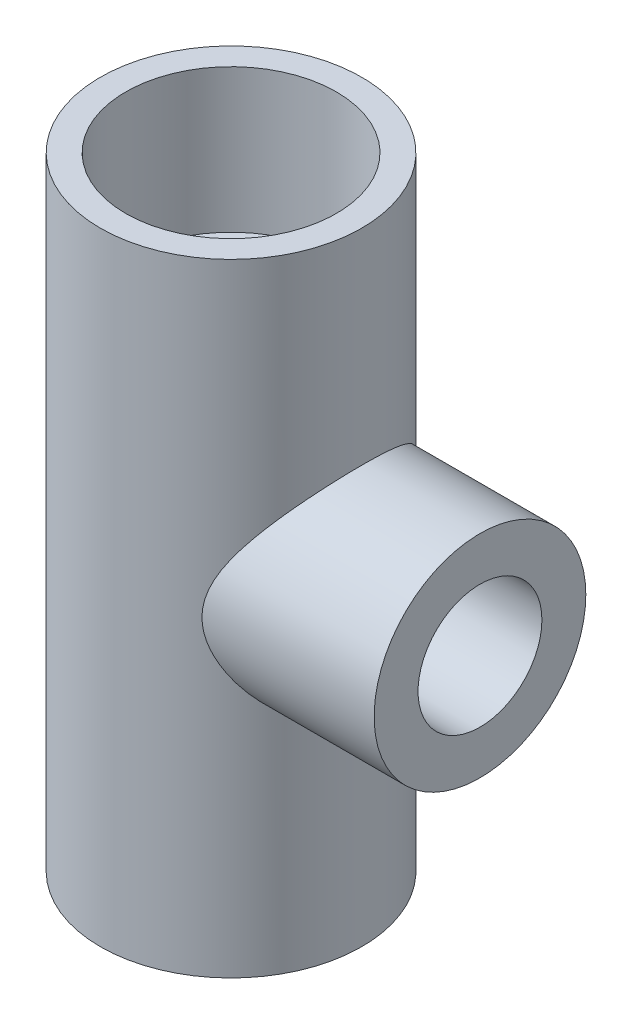
SolidWorks part; units mm, degrees
ref_plane "Front Plane" through (0, 0, 0) normal (0, 0, 1) x (1, 0, 0)
ref_plane "Top Plane" through (0, 0, 0) normal (0, 1, 0) x (1, 0, 0)
ref_plane "Right Plane" through (0, 0, 0) normal (1, 0, 0) x (0, 0, -1)
sketch "Sketch1" plane through (0, 0, 0) normal (0, 1, 0) x (1, 0, 0)
  circle A0 centre (0, 0) radius 0.6565
  circle A1 centre (0, 0) radius 0.529
  circle A2 centre (0, 0) radius 0.412
  dimension "D1" = 1.313
  dimension "D2" = 1.058
  dimension "D3" = 0.824
extrude "Boss-Extrude1" add sketch "Sketch1" along normal blind 1.5625 contours A0 A1 | A1 A2 region at (-0.6379, 0, 0) region at (-0.514, 0, 0)
extrude "Cut-Extrude1" cut sketch "Sketch1<3>" along normal blind 0.72 contours A1 A2 region at (-0.514, 0, 0)
sketch "Sketch1<3>" plane through (0, 0, 0) normal (0, 1, 0) x (1, 0, 0) same geometry as "Sketch1"
mirror "Mirror1" about plane through (0, 1.5625, 0) normal (0, 1, 0) of "Cut-Extrude1", "Boss-Extrude1"
ref_plane "Plane1" through (1.25, 0, 0) normal (1, 0, 0) x (0, 0, -1)
sketch "Sketch2" plane through (1.25, 0, 0) normal (1, 0, 0) x (0, 0, -1)
  line L0 (0, 3.125) -> (0, 0) construction
  line L1 (0.6565, 3.125) -> (-0.6565, 3.125) construction
  line L2 (-0.6565, 0) -> (0.6565, 0) construction
  circle A0 centre (0, 1.5625) radius 0.5315
  circle A1 centre (0, 1.5625) radius 0.424
  circle A2 centre (0, 1.5625) radius 0.311
  dimension "D1" = 1.063
  dimension "D2" = 0.848
  dimension "D3" = 0.622
extrude "Boss-Extrude2" add sketch "Sketch2" against normal up to surface (0.8646 mm away) contours L0 A0 A1 | L0 A1 A2 | A1 L0 A2 | A0 L0 A1 region at (1.25, 1.9299, -0.3674) region at (1.25, 2.0403, 0.0119) region at (1.25, 1.8556, -0.2931) region at (1.25, 1.93, 0.0095) up to face at (0, 0, 0.6565)
extrude "Cut-Extrude2" cut sketch "Sketch2<3>" against normal up to next contours A2 L0 | L0 A2 region at (1.25, 1.5625, -0.132) region at (1.25, 1.5625, 0.132)
sketch "Sketch2<3>" plane through (1.25, 0, 0) normal (1, 0, 0) x (0, 0, -1) same geometry as "Sketch2"
